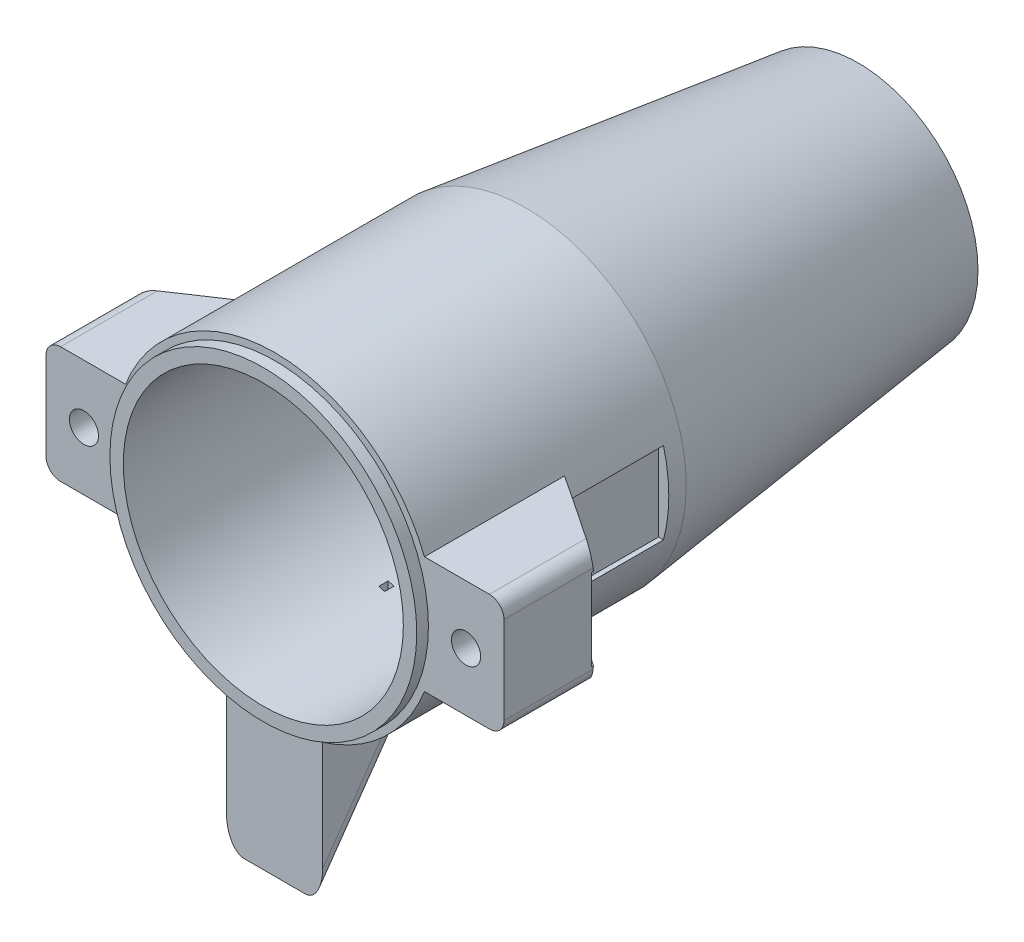
SolidWorks part; units mm, degrees
ref_plane "Front Plane" through (0, 0, 0) normal (0, 0, 1) x (1, 0, 0)
ref_plane "Top Plane" through (0, 0, 0) normal (0, 1, 0) x (1, 0, 0)
ref_plane "Right Plane" through (0, 0, 0) normal (1, 0, 0) x (0, 0, -1)
sketch "Sketch1" plane through (0, 0, 0) normal (0, 0, 1) x (1, 0, 0)
  circle A0 centre (0, 0) radius 12
  circle A1 centre (0, 0) radius 13.75
extrude "Boss-Extrude1" add sketch "Sketch1" against normal blind 50
sketch "Sketch2" plane through (0, 0, 0) normal (0, 0, 1) x (1, 0, 0)
  line L0 (-12.8087, 5) -> (-19.625, 5)
  line L1 (-19.625, 5) -> (-19.625, -5)
  line L2 (-19.625, -5) -> (-12.8087, -5)
  line L3 (0, 13.75) -> (0, -13.75) construction
  line L4 (19.625, -5) -> (12.8087, -5)
  line L5 (19.625, 5) -> (19.625, -5)
  line L6 (12.8087, 5) -> (19.625, 5)
  line L7 (-12.8087, -5) -> (-12.8087, 5) construction
  circle A1 centre (-16.375, 0) radius 1.25
  circle A2 centre (0, 0) radius 13.75 construction
  circle A3 centre (16.375, 0) radius 1.25
  circle A4 centre (0, 0) radius 13.75
  point P8 (-19.625, 0)
  point P11 (0, 0)
  point P22 (0, 0)
  point P23 (0, 0)
  point P24 (0, 0)
  circle M2 centre (0, 0) radius 13.75
extrude "Boss-Extrude2" add sketch "Sketch2" against normal blind 7.5 contours L1 L2 L0 A1 M2 | L6 L4 L5 A3 M2
sketch "Sketch4" plane through (0, 0, -50) normal (0, 0, -1) x (-1, 0, 0)
  circle A0 centre (0, 0) radius 13.25
extrude "Boss-Extrude3" add sketch "Sketch4" against normal blind 20
sketch "Sketch8" plane through (0, 0, -30) normal (0, 0, 1) x (1, 0, 0)
  circle A0 centre (0, 0) radius 5.2
extrude "Cut-Extrude2" cut sketch "Sketch8" against normal up to surface (20 mm away) up to face at (13.75, 0, -50)
chamfer "Chamfer2" distance 2.8 angle 81.75 1 edges at (5.2, 0, -30)
sketch3d "3DSketch3"
  line L1 (-5, -13.8, -11) -> (5, -13.8, -11)
  line L2 (-5, -13.8, -11) -> (-5, -13.8, -19)
  line L3 (-5, -13.8, -19) -> (5, -13.8, -19)
  line L4 (5, -13.8, -11) -> (5, -13.8, -19)
  line L5 (-5, -13.8, -11) -> (5, -13.8, -19) construction
  line L6 (-5, -13.8, -19) -> (5, -13.8, -11) construction
  point P0 (0, -13.8, -15)
  point P5 (0, 0, 0)
  point P6 (0, 0, 0)
extrude "Boss-Extrude4" add sketch "3DSketch3" along direction (0, 1, 0) on the side against the normal up to surface (0.9913 mm away)
sketch "Sketch9" plane through (0, -13.8, 0) normal (0, -1, 0) x (1, 0, 0)
  line L1 (-3.1, -11.9) -> (3.1, -11.9)
  line L2 (-3.1, -11.9) -> (-3.1, -18.1)
  line L3 (-3.1, -18.1) -> (3.1, -18.1)
  line L4 (3.1, -11.9) -> (3.1, -18.1)
  line L5 (-3.1, -11.9) -> (3.1, -18.1) construction
  line L6 (-3.1, -18.1) -> (3.1, -11.9) construction
  point P0 (0, -15)
  point P5 (0, 0)
  point P6 (0, 0)
extrude "Cut-Extrude3" cut sketch "Sketch9" against normal blind 1.2
sketch "Sketch10" plane through (0, -13.8, 0) normal (0, -1, 0) x (1, 0, 0)
  line L0 (-5, -15) -> (5, -15) construction
  line L1 (2.95, -12.35) -> (3.45, -12.35)
  line L2 (2.95, -12.35) -> (2.95, -13.15)
  line L3 (2.95, -13.15) -> (3.45, -13.15)
  line L4 (3.45, -12.35) -> (3.45, -13.15)
  line L5 (2.95, -12.35) -> (3.45, -13.15) construction
  line L6 (2.95, -13.15) -> (3.45, -12.35) construction
  line L7 (-5, -19) -> (-5, -11) construction
  line L8 (5, -11) -> (5, -19) construction
  line L9 (0, -11) -> (0, -19) construction
  line L10 (-5, -11) -> (5, -11) construction
  line L11 (5, -19) -> (-5, -19) construction
  line L12 (-2.95, -13.15) -> (-3.45, -13.15)
  line L13 (-3.45, -12.35) -> (-3.45, -13.15)
  line L14 (-2.95, -12.35) -> (-3.45, -12.35)
  line L15 (-2.95, -12.35) -> (-2.95, -13.15)
  line L16 (2.95, -16.85) -> (3.45, -16.85)
  line L17 (3.45, -17.65) -> (3.45, -16.85)
  line L18 (2.95, -17.65) -> (3.45, -17.65)
  line L19 (2.95, -17.65) -> (2.95, -16.85)
  line L20 (-2.95, -16.85) -> (-3.45, -16.85)
  line L21 (-2.95, -17.65) -> (-2.95, -16.85)
  line L22 (-2.95, -17.65) -> (-3.45, -17.65)
  line L23 (-3.45, -17.65) -> (-3.45, -16.85)
  point P0 (3.2, -12.75)
  point P17 (0, 0)
  point P18 (0, 0)
  point P31 (0, 0)
  point P32 (0, 0)
  point P33 (0, 0)
  dimension "D1" = 0.8
  dimension "D2" = 0.5
extrude "Cut-Extrude4" cut sketch "Sketch10" against normal up to surface (2.3066 mm away)
sketch "Sketch11" plane through (0, 0, 0) normal (0, 0, 1) x (1, 0, 0)
  circle A0 centre (0, 0) radius 12
  circle A1 centre (0, 0) radius 13.15
extrude "Boss-Extrude5" add sketch "Sketch11" along normal blind 1
chamfer "Chamfer4" distance 1 angle 45 2 edges
sketch "Sketch12" plane through (0, 0, 0) normal (0, 0, 1) x (1, 0, 0)
  line L1 (-4.1618, -25.1282) -> (4.0882, -25.1282)
  line L2 (-4.1618, -25.1282) -> (-4.1618, -13.1282)
  line L3 (-4.1618, -13.1282) -> (4.0882, -13.1282)
  line L4 (4.0882, -25.1282) -> (4.0882, -13.1282)
  line L5 (-4.1618, -25.1282) -> (4.0882, -13.1282) construction
  line L6 (-4.1618, -13.1282) -> (4.0882, -25.1282) construction
  circle A0 centre (0, 0) radius 13.75 construction
  point P0 (-0.0368, -19.1282)
  point P6 (0, 0)
  point P7 (0, 0)
  point P9 (0, 0)
extrude "Boss-Extrude6" add sketch "Sketch12" against normal blind 8.5
chamfer "Chamfer5" distance 8.5 angle 55 1 edges at (-0.0368, -25.1282, -8.5)
fillet "Fillet3" radius 1.5 2 edges at (-4.1618, -19.1282, -4.2012) (4.0882, -19.1282, -4.2012)
sketch "Sketch13" plane through (0, 0, -7.5) normal (0, 0, -1) x (-1, 0, 0)
  line L1 (-19.875, 3.5) -> (-12.875, 3.5)
  line L2 (-19.875, 3.5) -> (-19.875, -3.5)
  line L3 (-19.875, -3.5) -> (-12.875, -3.5)
  line L4 (-12.875, 3.5) -> (-12.875, -3.5)
  line L5 (-19.875, 3.5) -> (-12.875, -3.5) construction
  line L6 (-19.875, -3.5) -> (-12.875, 3.5) construction
  line L7 (12.875, 3.5) -> (19.875, 3.5)
  line L8 (12.875, 3.5) -> (12.875, -3.5)
  line L9 (12.875, -3.5) -> (19.875, -3.5)
  line L10 (19.875, 3.5) -> (19.875, -3.5)
  line L11 (12.875, 3.5) -> (19.875, -3.5) construction
  line L12 (12.875, -3.5) -> (19.875, 3.5) construction
  point P0 (-16.375, 0)
  point P6 (16.375, 0)
extrude "Cut-Extrude5" cut sketch "Sketch13" along normal blind 12.5
chamfer "Chamfer6" distance 4.5 angle 55 4 edges at (-13.0744, -4.257, -7.5) (-13.0744, 4.257, -7.5) (13.0744, -4.257, -7.5) (13.0744, 4.257, -7.5)
chamfer "Chamfer3" distance 3.5 angle 83 1 edges at (13.75, 0, -50)
fillet "Fillet4" radius 1.25 4 edges at (-19.625, -5, -3.75) (-19.625, 5, -3.75) (19.625, 5, -3.75) (19.625, -5, -3.75)
